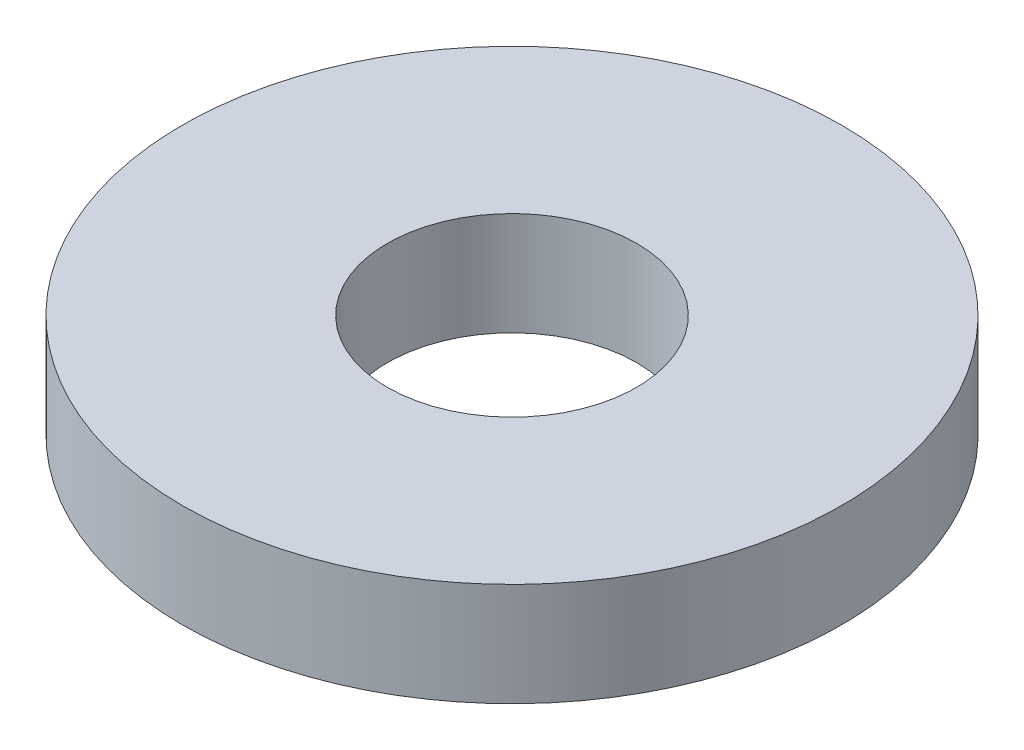
SolidWorks part; units mm, degrees
ref_plane "Front Plane" through (0, 0, 0) normal (0, 0, 1) x (1, 0, 0)
ref_plane "Top Plane" through (0, 0, 0) normal (0, 1, 0) x (1, 0, 0)
ref_plane "Right Plane" through (0, 0, 0) normal (1, 0, 0) x (0, 0, -1)
sketch "Sketch1" plane through (0, 0, 0) normal (0, 1, 0) x (1, 0, 0)
  circle A0 centre (0, 0) radius 92.5
  dimension "FLANGE_OD" = 185
extrude "Boss-Extrude1" add sketch "Sketch1" along normal blind 29
sketch "Sketch2" plane through (0, 0, 0) normal (0, 1, 0) x (1, 0, 0)
  circle A0 centre (0, 0) radius 35
  dimension "BORE_D" = 70
extrude "Cut-Extrude1" cut sketch "Sketch2" along normal through all
sketch "Sketch3" plane through (0, 29, 0) normal (0, 1, 0) x (1, 0, 0)
  circle A0 centre (0, 0) radius 23.8844 construction
  circle A1 centre (-23.8844, 0) radius 6.0201
  dimension "BOLT_D" = 12.0402
  dimension "BOLT_PCD" = 47.7688
extrude "Cut-Extrude2" cut sketch "Sketch3" against normal blind 26.7777 rebuild error yes
pattern_circular "CirPattern1" count 3 over 360 rebuild error yes
